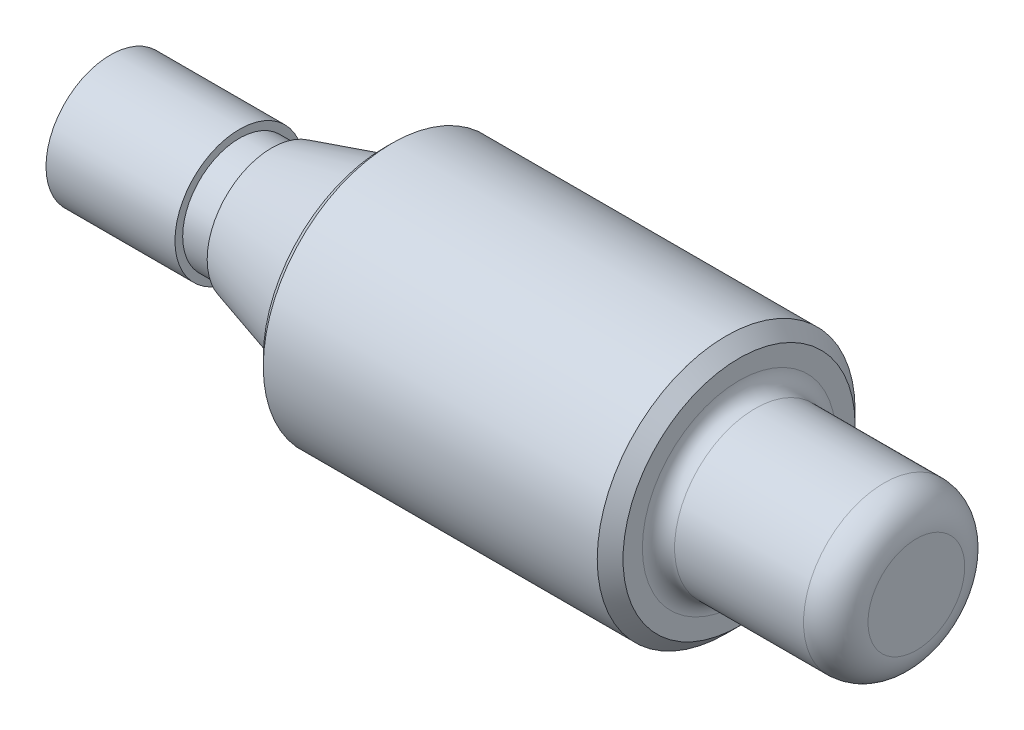
SolidWorks part; units mm, degrees
ref_plane "Front Plane" through (0, 0, 0) normal (0, 0, 1) x (1, 0, 0)
ref_plane "Top Plane" through (0, 0, 0) normal (0, 1, 0) x (1, 0, 0)
ref_plane "Right Plane" through (0, 0, 0) normal (1, 0, 0) x (0, 0, -1)
sketch "Sketch2" plane through (0, 0, 0) normal (1, 0, 0) x (0, 0, -1)
  circle A0 centre (0, 0) radius 12.7
extrude "Boss-Extrude1" add sketch "Sketch2" along normal blind 39.6875 and the other way blind 39.6875
sketch "Sketch3" plane through (39.6875, 0, 0) normal (1, 0, 0) x (0, 0, -1)
  circle A0 centre (0, 0) radius 7.9375
extrude "Cut-Extrude1" cut sketch "Sketch3" against normal blind 17.4625 flip side to cut
fillet "Fillet1" radius 3.175 1 edges at (39.6875, 0, -7.9375)
fillet "Fillet2" radius 1.5875 1 edges at (22.225, 0, -7.9375)
chamfer "Chamfer1" distance 1.27 angle 45 1 edges at (22.225, 0, -12.7)
sketch "Sketch4" plane through (-39.6875, 0, 0) normal (-1, 0, 0) x (0, 0, 1)
  circle A0 centre (0, 0) radius 6.35
extrude "Cut-Extrude2" cut sketch "Sketch4" against normal blind 12.7 flip side to cut
cosmetic thread "Cosmetic Thread1" parameters "D1"=12.7, "D2"=11.1887
sketch "Sketch6" plane through (-26.9875, 0, 0) normal (-1, 0, 0) x (0, 0, 1)
  circle A0 centre (0, 0) radius 5.588
extrude "Cut-Extrude3" cut sketch "Sketch6" against normal blind 3.175 flip side to cut
sketch "Sketch12" plane through (-23.8125, 0, 0) normal (-1, 0, 0) x (0, 0, 1)
  circle A0 centre (0, 0) radius 6.35
sketch "Sketch13" plane through (0, 0, 0) normal (0, 0, 1) x (1, 0, 0)
  line L0 (-23.8125, 6.35) -> (-12.7, 9.525)
  line L1 (-23.8125, 6.35) -> (-23.8125, -6.35) construction
  line L2 (-12.7, 9.525) -> (-12.7, 12.7)
  line L3 (20.955, 12.7) -> (-23.8125, 12.7) construction
  line L4 (-12.7, 12.7) -> (-23.8125, 12.7)
  line L5 (-23.8125, 12.7) -> (-23.8125, 6.35)
ref_axis "Axis1" through (-43.6562, 0, 0) along (1, 0, 0)
revolve "Cut-Revolve1" cut sketch "Sketch13" angle 360 about axis through (-43.6562, 0, 0) along (1, 0, 0)
fillet "Fillet3" radius 1.27 1 edges at (-12.7, 0, 9.525)
chamfer "Chamfer2" distance 0.762 angle 45 1 edges at (-12.7, 0, 12.7)
